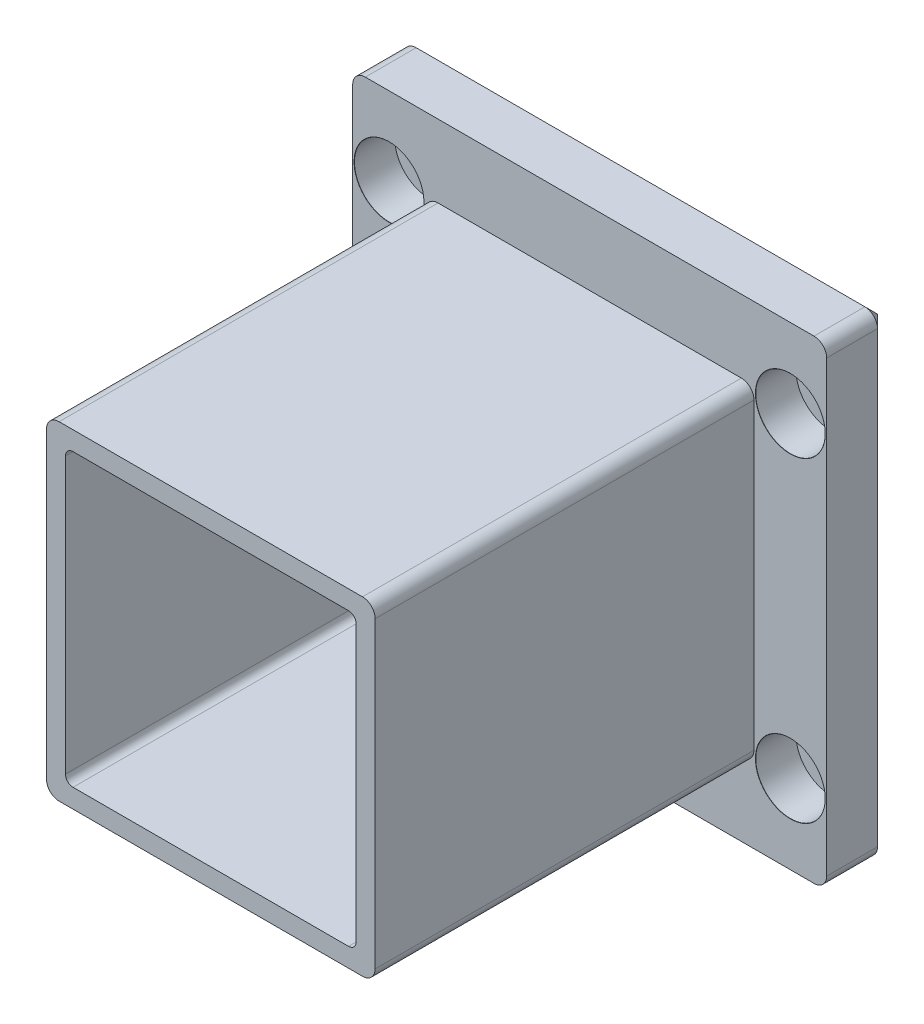
SolidWorks part; units mm, degrees
ref_plane "Front Plane" through (0, 0, 0) normal (1, 0, 0) x (0, 1, 0)
ref_plane "Top Plane" through (0, 0, 0) normal (0, 0, 1) x (0, 1, 0)
ref_plane "Right Plane" through (0, 0, 0) normal (0, 1, 0) x (-1, 0, 0)
sketch "Sketch1" plane through (0, 0, 0) normal (0, 0, 1) x (0, 1, 0)
  line L0 (-29.048, 30.1461) -> (-26.1566, 30.1461)
  line L1 (-29.048, 30.1461) -> (22.952, 30.1461)
  line L2 (-29.048, 30.1461) -> (-29.048, -21.8539)
  line L3 (-29.048, -21.8539) -> (22.952, -21.8539)
  line L4 (22.952, 30.1461) -> (22.952, -21.8539)
  line L6 (22.952, 30.1461) -> (15.3397, 30.1461)
  line L8 (-26.048, 27.1461) -> (-26.048, -18.8539)
  line L9 (-26.048, -18.8539) -> (19.952, -18.8539)
  line L10 (19.952, 27.1461) -> (19.952, -18.8539)
  line L11 (-26.048, 27.1461) -> (19.952, 27.1461)
  dimension "D1" = 46
  dimension "D2" = 46
  dimension "D3" = 3
extrude "Boss-Extrude1" add sketch "Sketch1" along normal blind 65 contours L4 L1 L0 L2 L3 L8 L11 L10 L9 region at (-29.4107, -27.6023, 0)
sketch "Sketch3" plane through (0, 0, 0) normal (0, 0, -1) x (1, 0, 0)
  line L0 (-4.1461, 29.048) -> (-4.1461, -22.952)
  line L1 (-30.1461, 29.048) -> (21.8539, 29.048) construction
  line L2 (-30.1461, -22.952) -> (21.8539, -22.952) construction
  line L3 (21.8539, 29.048) -> (33.3539, 40.548)
  line L4 (-41.6461, 40.548) -> (33.3539, 40.548)
  line L5 (-41.6461, 40.548) -> (-41.6461, -34.452)
  line L6 (-41.6461, -34.452) -> (33.3539, -34.452)
  line L7 (33.3539, 40.548) -> (33.3539, -34.452)
  line L8 (-41.6461, 40.548) -> (33.3539, -34.452) construction
  line L9 (-41.6461, -34.452) -> (33.3539, 40.548) construction
  line L10 (27.6039, -21.952) -> (27.6039, 28.048)
  line L11 (27.6039, -28.702) -> (27.6039, 34.798)
  line L12 (-29.1461, 34.798) -> (20.8539, 34.798)
  line L13 (-35.8961, -21.952) -> (-35.8961, 28.048)
  line L14 (20.8539, -28.702) -> (-29.1461, -28.702)
  point P6 (-4.1461, 3.048)
  point P22 (27.6039, 3.048)
  line M5 (-30.1461, -22.952) -> (21.8539, -22.952)
  line M6 (21.8539, -22.952) -> (21.8539, 29.048)
  line M7 (21.8539, 29.048) -> (-30.1461, 29.048)
  line M8 (-30.1461, 29.048) -> (-30.1461, -22.952)
  line M9 (-27.1461, 26.048) -> (18.8539, 26.048)
  line M10 (18.8539, 26.048) -> (18.8539, -19.952)
  line M11 (18.8539, -19.952) -> (-27.1461, -19.952)
  line M12 (-27.1461, -19.952) -> (-27.1461, 26.048)
  dimension "D1" = 50
  dimension "D2" = 75
extrude "Boss-Extrude2" add sketch "Sketch3" along normal blind 5 contours L0 M9 M12 M11 | L0 M9 M11 M10 | L0 M7 M8 M5 M11 M12 M9 | L0 M7 M9 M10 M11 M5 M6 | L7 L4 L5 L6 M5 M8 M7 M6 | L5 L4 L7 L6 region at (8.8539, -28.4666, 0) region at (32.2932, -3.048, 0) region at (-4.7275, -27.548, 0) region at (7.3539, -3.048, 0) region at (-15.6461, -3.048, 0)
sketch "Sketch8" plane through (0, 0, 0) normal (0, 0, 1) x (1, 0, 0)
  line L1 (-41.6461, 34.452) -> (33.3539, 34.452)
  line L2 (-41.6461, 34.452) -> (-41.6461, -40.548)
  line L3 (-41.6461, -40.548) -> (33.3539, -40.548)
  line L4 (33.3539, 34.452) -> (33.3539, -40.548)
  line L5 (-30.1461, 22.952) -> (21.8539, 22.952)
  line L6 (-30.1461, 22.952) -> (-30.1461, -29.048)
  line L7 (-30.1461, -29.048) -> (21.8539, -29.048)
  line L8 (21.8539, 22.952) -> (21.8539, -29.048)
extrude "Boss-Extrude3" add sketch "Sketch8" along normal blind 5.0471
fillet "Fillet1" radius 2 8 edges at (21.8539, -29.048, 35.0235) (-30.1461, -29.048, 35.0235) (-30.1461, 22.952, 35.0235) (21.8539, 22.952, 35.0235) (33.3539, 34.452, 0.0235) (-41.6461, 34.452, 0.0235) (-41.6461, -40.548, 0.0235) (33.3539, -40.548, 0.0235)
sketch "Sketch13" plane through (0, 0, 5.0471) normal (0, 0, 1) x (1, 0, 0)
  line L0 (-35.8961, 21.952) -> (-35.8961, -28.048)
  line L1 (-29.1461, -34.798) -> (20.8539, -34.798)
  line L2 (-41.6461, 34.452) -> (33.3539, -40.548)
  line L3 (27.6039, 21.952) -> (27.6039, -28.048)
  line L4 (-29.1461, 28.702) -> (20.8539, 28.702)
  point P0 (-35.8961, 21.952)
  point P1 (-35.8961, -28.048)
  point P12 (27.6039, 21.952)
  point P13 (27.6039, -28.048)
hole_wizard "CBORE for M6 Hex Socket Head Cap Screw2" positions "Sketch13" profile "Sketch15" counterbore size "M6" standard "ISO" end condition through all
sketch "Sketch15" plane through (-35.8961, 21.952, 5.0471) normal (1, 0, 0) x (0, -1, 0)
  line L0 (0, 0) -> (0, 10.0471)
  line L1 (0, 10.0471) -> (3.3, 10.0471)
  line L3 (3.3, 10.0471) -> (3.3, 6.4)
  line L4 (5.5, 6.4) -> (3.3, 6.4)
  line L5 (5.5, 6.4) -> (5.5, 0.025)
  line L6 (5.5, 0.025) -> (5.525, 0)
  line L7 (5.525, 0) -> (0, 0)
  line L8 (-5.5, 0.025) -> (-5.525, 0) construction
  line L11 (0, -6.35) -> (0, 107.95) construction
  dimension "Thru Hole Dia." = 6.6
  dimension "Thru Hole Depth" = 10.0471
  dimension "C'Bore Dia." = 11
  dimension "C'Bore Depth" = 6.4
  dimension "Near C'Sink Dia." = 11.05
  dimension "Near C'Sink Angle" = 90
chamfer "Chamfer2" distance 2 angle 45 8 edges at (-41.6461, -3.048, -5) (-4.1461, -40.548, -5) (33.3539, -3.048, -5) (-41.0603, -39.9622, -5) (32.7681, -39.9622, -5) (-41.0603, 33.8662, -5) (32.7681, 33.8662, -5) (-4.1461, 34.452, -5)
fillet "Fillet2" radius 1.2 4 edges at (18.8539, 19.952, 32.5) (-27.1461, 19.952, 32.5) (-27.1461, -26.048, 32.5) (18.8539, -26.048, 32.5)
